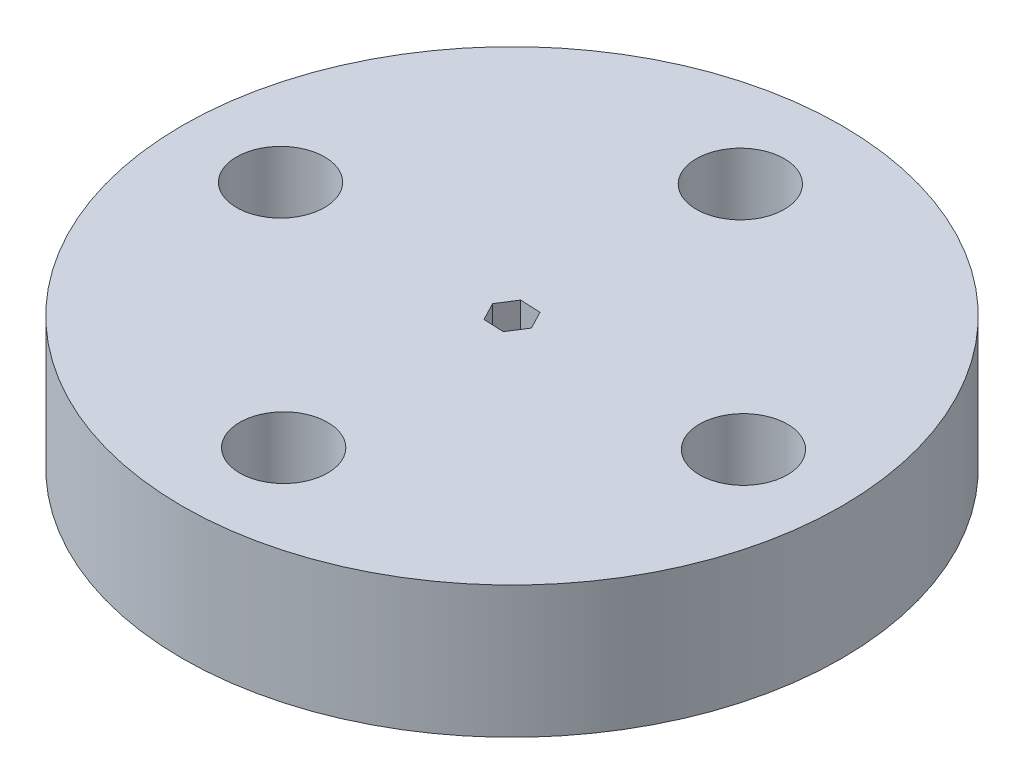
SolidWorks part; units mm, degrees
ref_plane "Front Plane" through (0, 0, 0) normal (0, 0, 1) x (1, 0, 0)
ref_plane "Top Plane" through (0, 0, 0) normal (0, 1, 0) x (1, 0, 0)
ref_plane "Right Plane" through (0, 0, 0) normal (1, 0, 0) x (0, 0, -1)
sketch "Sketch1" plane through (0, 0, 0) normal (0, 1, 0) x (1, 0, 0)
  line L0 (0, 75) -> (0, -75) construction
  line L1 (-75, 0) -> (75, 0) construction
  circle A0 centre (0, 0) radius 75
  circle A1 centre (0, -51.9403) radius 10
  circle A2 centre (52.6486, 0) radius 10
  circle A3 centre (-52.6486, 0) radius 10
  circle A4 centre (0, 51.9403) radius 10
extrude "Boss-Extrude1" add sketch "Sketch1" against normal blind 30
sketch "Sketch2" plane through (0, -30, 0) normal (0, -1, 0) x (1, 0, 0)
  circle A0 centre (0, 0) radius 20
extrude "Boss-Extrude2" add sketch "Sketch2" along normal blind 30
sketch "Sketch3" plane through (0, -60, 0) normal (0, -1, 0) x (1, 0, 0)
  line L1 (2.1309, 4.0979) -> (-2.4834, 3.8944)
  line L2 (-2.4834, 3.8944) -> (-4.6143, -0.2035)
  line L3 (-4.6143, -0.2035) -> (-2.1309, -4.0979)
  line L4 (-2.1309, -4.0979) -> (2.4834, -3.8944)
  line L5 (2.4834, -3.8944) -> (4.6143, 0.2035)
  line L6 (4.6143, 0.2035) -> (2.1309, 4.0979)
  circle A0 centre (0, 0) radius 4 construction
extrude "Boss-Extrude5" add sketch "Sketch3" against normal through all
extrude "Cut-Extrude1" cut sketch "Sketch3<3>" against normal through all
sketch "Sketch3<3>" plane through (0, -60, 0) normal (0, -1, 0) x (1, 0, 0) same geometry as "Sketch3"
